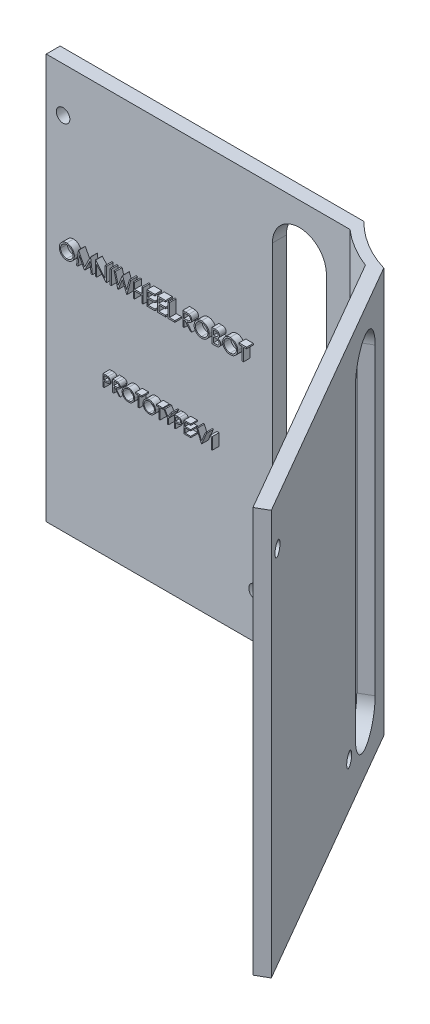
SolidWorks part; units mm, degrees
ref_plane "Plan de face" through (0, 0, 0) normal (0, 0, 1) x (1, 0, 0)
ref_plane "Plan de dessus" through (0, 0, 0) normal (0, 1, 0) x (1, 0, 0)
ref_plane "Plan de droite" through (0, 0, 0) normal (1, 0, 0) x (0, 0, -1)
sketch "Esquisse3" plane through (0, 0, 0) normal (0, 1, 0) x (1, 0, 0)
  line L0 (-150.1573, 0) -> (189.6273, 0) construction
  line L1 (-83.8395, -145.9242) -> (87.7229, 151.2306) construction
  line L2 (-78.0725, 135.2255) -> (117.7517, -203.9519) construction
  line L3 (-125, 131.2995) -> (-125, -153.5705) construction
  line L4 (-25, -24.4949) -> (-115, -24.4949)
  line L6 (-21.2883, 25.5051) -> (-23.9685, 25.5051)
  line L7 (-115, -24.4949) -> (-115, 25.5051)
  line L8 (-25, -24.4949) -> (-115, 25.5051) construction
  line L9 (-21.2883, 25.5051) -> (-115, -24.4949) construction
  line L10 (-23.9685, 25.5051) -> (-115, 25.5051)
  line L11 (34.0723, 8.0048) -> (79.5881, 86.8404)
  line L12 (36.2868, 111.8404) -> (79.5881, 86.8404)
  line L13 (-8.7132, 33.8981) -> (36.2868, 111.8404)
  line L14 (-10.1038, -33.5099) -> (35.4119, -112.3455)
  line L15 (78.7132, -87.3455) -> (35.4119, -112.3455)
  line L16 (33.7132, -9.4032) -> (78.7132, -87.3455)
  line L17 (-23.9685, 25.5051) -> (-25, -24.4949)
  line L18 (-8.7132, 33.8981) -> (34.0723, 8.0048)
  line L19 (-10.1038, -33.5099) -> (33.7132, -9.4032)
  line L20 (-25, -28.6182) -> (-115, -28.6182)
  line L21 (-115, -28.6182) -> (-115, -24.4949)
  line L22 (-13.5526, -35.5011) -> (31.9631, -114.3367)
  line L23 (31.9631, -114.3367) -> (35.4119, -112.3455)
  circle A0 centre (0, 0) radius 125
  circle A1 centre (0, 0) radius 35
  circle A2 centre (0, 0) radius 125
  circle A3 centre (0, 0) radius 125
  circle A4 centre (0, 0) radius 38
  point P9 (-69.0908, 0)
  point P32 (0, 0)
  dimension "D1" = 250
  dimension "D4" = 70
  dimension "D2" = 120
  dimension "D3" = 120
  dimension "D5" = 10
  dimension "D6" = 50
  dimension "D7" = 90
  dimension "D9" = 3
  dimension "D8" = 3
extrude "Boss.-Extru.1" add sketch "Esquisse3" along normal blind 120 contours A4 L4 L21 L20 | L4 A4 L14 A1 | A4 L22 L23 L14 region at (-18.6168, 0, 30.8794) region at (-71.0566, 0, 26.5723) region at (11.4638, 0, 74.8797)
sketch "Esquisse4" plane through (0, 0, 28.6182) normal (0, 0, 1) x (1, 0, 0)
  line L0 (-40, 120) -> (-40, 0) construction
  line L1 (-25, 120) -> (-115, 120) construction
  line L2 (-25, 0) -> (-115, 0) construction
  line L3 (-48, 105) -> (-48, 15)
  line L4 (-25, 120) -> (-25, 0) construction
  line L5 (-115, 60) -> (-20.315, 60) construction
  line L6 (-115, 120) -> (-115, 0) construction
  line L7 (-32, 105) -> (-32, 15)
  arc A0 (-48, 15) -> (-32, 15) centre (-40, 15) ccw
  arc A1 (-48, 105) -> (-32, 105) centre (-40, 105) cw
  dimension "D1" = 8
  dimension "D2" = 15
  dimension "D3" = 45
  dimension "D4" = 45
extrude "Enlèv. mat.-Extru.1" cut sketch "Esquisse4" against normal through all
sketch "Esquisse5" plane through (-25.5369, 0, 14.7437) normal (-0.866, 0, 0.5) x (0.5, 0, 0.866)
  line L0 (38.9685, 120) -> (38.9685, 0) construction
  line L1 (23.9685, 120) -> (115, 120) construction
  line L2 (46.9685, 105) -> (46.9685, 15)
  line L3 (38.9685, 60) -> (127.8483, 60) construction
  line L4 (115, 120) -> (115, 0) construction
  line L5 (23.9685, 120) -> (23.9685, 0) construction
  line L6 (30.9685, 105) -> (30.9685, 15)
  arc A0 (46.9685, 15) -> (30.9685, 15) centre (38.9685, 15) cw
  arc A1 (46.9685, 105) -> (30.9685, 105) centre (38.9685, 105) ccw
  point P14 (115, 60)
  dimension "D1" = 8
  dimension "D2" = 45
  dimension "D3" = 45
  dimension "D4" = 15
extrude "Enlèv. mat.-Extru.2" cut sketch "Esquisse5" against normal through all
sketch "Esquisse6" plane through (0, 0, 28.6182) normal (0, 0, 1) x (1, 0, 0)
  circle A0 centre (-110, 106.75) radius 2 construction
  circle A1 centre (-110, 106.75) radius 2
sketch "Esquisse7" plane through (-25.5369, 0, 14.7437) normal (-0.866, 0, 0.5) x (0.5, 0, 0.866)
  circle A0 centre (110, 106.75) radius 2 construction
  circle A1 centre (110, 106.75) radius 2
extrude "Enlèv. mat.-Extru.3" cut sketch "Esquisse6" against normal through all
extrude "Enlèv. mat.-Extru.4" cut sketch "Esquisse7" against normal through all
sketch "Esquisse8" plane through (0, 0, 28.6182) normal (0, 0, 1) x (1, 0, 0)
  line L0 (-115, 72.2203) -> (-48, 72.2203) construction
  line L1 (-107.7615, 44.975) -> (-51.4576, 44.975) construction
  line L2 (-115, 120) -> (-115, 0) construction
  line L3 (-48, 105) -> (-48, 15) construction
  text T0 "OMNIWHEEL ROBOT" font "Century Gothic" height in points 16
  text T1 "PROTOTYPE V1" font "Century Gothic" height 3.5
  point P5 (-45.4159, 71.9005)
  point P6 (-115, 72.5379)
  point P9 (-48, 72.2203)
extrude "Boss.-Extru.2" add sketch "Esquisse8" along normal blind 2
sketch "Esquisse9" plane through (0, 0, 28.6182) normal (0, 0, 1) x (1, 0, 0)
  circle A0 centre (-53, 13) radius 2 construction
  circle A1 centre (-53, 13) radius 2
sketch "Esquisse10" plane through (-25.5369, 0, 14.7437) normal (-0.866, 0, 0.5) x (0.5, 0, 0.866)
  circle A0 centre (51.9685, 13) radius 2 construction
  circle A1 centre (51.9685, 13) radius 2
extrude "Enlèv. mat.-Extru.5" cut sketch "Esquisse9" against normal through all
extrude "Enlèv. mat.-Extru.6" cut sketch "Esquisse10" against normal through all
